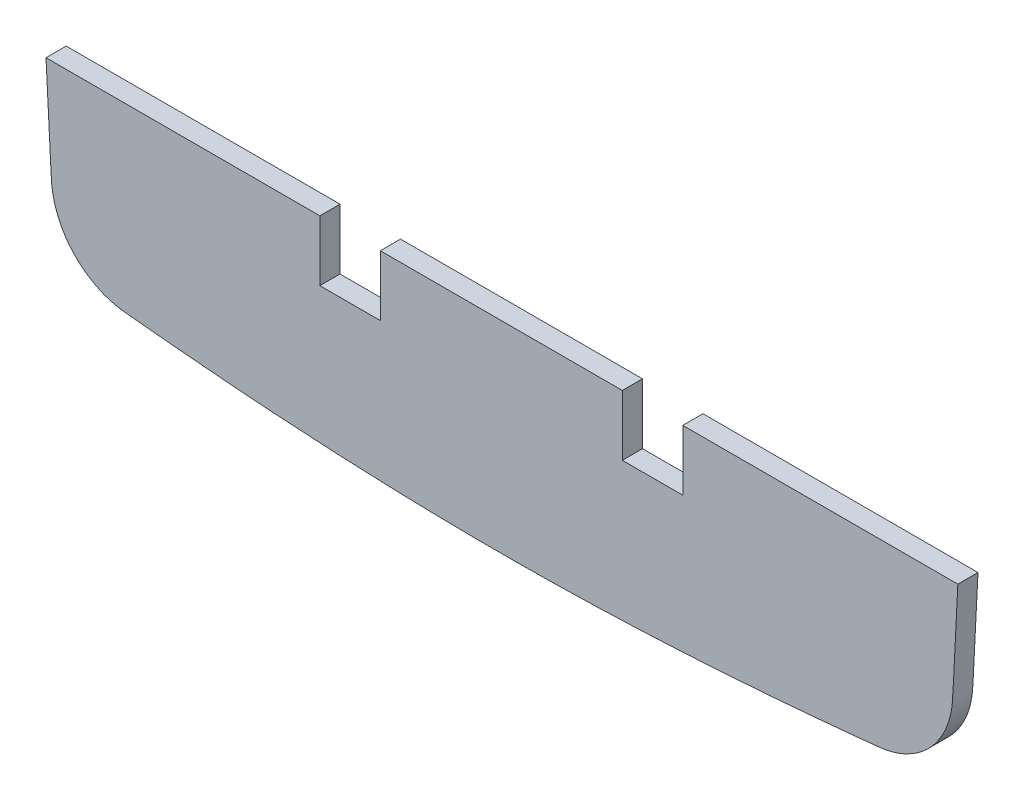
SolidWorks part; units mm, degrees
material "Balsa"
ref_plane "Front Plane" through (0, 0, 0) normal (0, 0, 1) x (1, 0, 0)
ref_plane "Top Plane" through (0, 0, 0) normal (0, 1, 0) x (1, 0, 0)
ref_plane "Right Plane" through (0, 0, 0) normal (1, 0, 0) x (0, 0, -1)
sketch "Sketch1" plane through (0, 0, 0) normal (0, 0, 1) x (1, 0, 0)
  line L0 (0, 0) -> (63.5, 0) construction
  line L1 (63.5, 0) -> (63.5, -63.8615) construction
  line L2 (63.5, 0) -> (63.5, 62.0279) construction
  line L3 (63.5, 0) -> (121.8493, 0) construction
  line L4 (5.9984, -38.4615) -> (121.0016, -38.4615)
  line L5 (48.26, -46.0815) -> (40.64, -38.4615) construction
  line L6 (78.74, -38.4615) -> (86.36, -38.4615)
  line L7 (78.74, -38.4615) -> (78.74, -46.0815)
  line L8 (78.74, -46.0815) -> (86.36, -46.0815)
  line L9 (86.36, -38.4615) -> (86.36, -46.0815)
  line L10 (78.74, -38.4615) -> (86.36, -46.0815) construction
  line L11 (78.74, -46.0815) -> (86.36, -38.4615) construction
  line L12 (48.26, -38.4615) -> (40.64, -46.0815) construction
  line L13 (40.64, -38.4615) -> (40.64, -46.0815)
  line L14 (48.26, -46.0815) -> (40.64, -46.0815)
  line L15 (48.26, -38.4615) -> (48.26, -46.0815)
  line L16 (48.26, -38.4615) -> (40.64, -38.4615)
  spline S0 degree 3 poles (63.5, 62.0279) (67.9841, 62.0313) (72.5689, 61.9603) (77.2546, 61.8087) (79.5975, 61.7328) (81.9656, 61.6369) (84.359, 61.5204) (85.5557, 61.4622) (86.7587, 61.3989) (87.9681, 61.3303) (88.5728, 61.2961) (89.1791, 61.2605) (89.787, 61.2237) (90.0909, 61.2052) (90.3952, 61.1865) (90.7, 61.1674) (90.8523, 61.1579) (91.0048, 61.1483) (91.2336, 61.1337) (91.3099, 61.1289) (91.4244, 61.1215) (91.4626, 61.1191) (91.5199, 61.1154) (91.539, 61.1142) (91.5676, 61.1123) (91.5772, 61.1117) (91.5962, 61.1105) (91.607, 61.1098) (91.6153, 61.1093) (95.9081, 60.8323) (100.3402, 60.4874) (104.9144, 60.0718) (106.0579, 59.9679) (107.2103, 59.8596) (108.3718, 59.7469) (108.9525, 59.6905) (109.5354, 59.6331) (110.1207, 59.5745) (110.4133, 59.5453) (110.7065, 59.5157) (111.0002, 59.4859) (111.1471, 59.471) (111.294, 59.457) (111.5891, 59.4207) (111.7372, 59.3991) (111.8856, 59.3739) (112.4793, 59.2732) (113.0782, 59.1159) (114.2582, 58.6819) (114.8392, 58.4041) (115.9535, 57.729) (116.4869, 57.3328) (116.981, 56.8846) (117.228, 56.6605) (117.4652, 56.4233) (117.6906, 56.174) (117.8033, 56.0494) (117.913, 55.9217) (118.0731, 55.7261) (118.1257, 55.6601) (118.2034, 55.5603) (118.2292, 55.5268) (118.2674, 55.4764) (118.2801, 55.4595) (118.2991, 55.4342) (118.3054, 55.4257) (118.3181, 55.4088) (118.3255, 55.3988) (118.3306, 55.3918) (118.9884, 54.5031) (119.5132, 53.4969) (119.8638, 52.437) (120.039, 51.9071) (120.1722, 51.3639) (120.2628, 50.8163) (120.3081, 50.5425) (120.3428, 50.2677) (120.3907, 49.7182) (120.4027, 49.444) (120.418, 49.1684) (120.5404, 46.9632) (120.6594, 44.6922) (120.8872, 40.0186) (120.996, 37.6159) (121.0977, 35.1473) (121.1486, 33.9131) (121.1977, 32.6623) (121.2448, 31.3952) (121.2683, 30.7616) (121.2914, 30.1239) (121.3139, 29.4822) (121.3251, 29.1613) (121.3363, 28.8394) (121.3472, 28.5165) (121.3527, 28.355) (121.3582, 28.1933) (121.3663, 27.9503) (121.369, 27.8693) (121.373, 27.7476) (121.3744, 27.707) (121.3764, 27.6461) (121.3771, 27.6258) (121.3781, 27.5954) (121.3784, 27.5852) (121.3789, 27.57) (121.3791, 27.5649) (121.3794, 27.5548) (121.3796, 27.5479) (121.3797, 27.5446) (121.4915, 24.1484) (121.6067, 20.0897) (121.6965, 15.3644) (121.7414, 13.0018) (121.7798, 10.4726) (121.8069, 7.7774) (121.8205, 6.4298) (121.8313, 5.0408) (121.8386, 3.6104) (121.8422, 2.8952) (121.845, 2.1697) (121.8469, 1.4339) (121.8478, 1.066) (121.8485, 0.6956) (121.8489, 0.3225) (121.8491, 0.136) (121.8493, -0.0512) (121.8495, -0.3329) (121.8495, -0.4269) (121.8495, -0.5683) (121.8495, -0.6154) (121.8495, -0.6862) (121.8495, -0.7098) (121.8495, -0.7452) (121.8495, -0.757) (121.8495, -0.7807) (121.8495, -0.7912) (121.8495, -0.8043) (121.8484, -7.4995) (121.7684, -13.2128) (121.6707, -17.9374) (121.6219, -20.2997) (121.5684, -22.4154) (121.5158, -24.2854) (121.4895, -25.2205) (121.4634, -26.0941) (121.438, -26.9066) (121.4254, -27.3128) (121.4129, -27.7038) (121.4006, -28.0794) (121.3945, -28.2673) (121.3885, -28.4513) (121.3795, -28.7216) (121.3765, -28.8107) (121.3721, -28.943) (121.3706, -28.9869) (121.3684, -29.0523) (121.3677, -29.074) (121.3666, -29.1066) (121.3662, -29.1174) (121.3657, -29.1336) (121.3655, -29.139) (121.3652, -29.1471) (121.3652, -29.1498) (121.365, -29.1539) (121.365, -29.1552) (121.3649, -29.1579) (121.3649, -29.158) (121.3648, -29.1606) (121.1857, -34.4616) (120.969, -39.4501) (120.7334, -44.1255) (120.6156, -46.4631) (120.4931, -48.7226) (120.3678, -50.9044) (120.3522, -51.1771) (120.3398, -51.4482) (120.2916, -51.991) (120.2571, -52.2624) (120.2122, -52.5325) (120.1225, -53.0727) (119.9915, -53.6079) (119.6485, -54.6514) (119.4358, -55.1596) (119.1855, -55.6466) (119.0603, -55.8901) (118.9259, -56.1283) (118.783, -56.3603) (118.7116, -56.4762) (118.638, -56.5907) (118.5246, -56.7599) (118.4863, -56.8158) (118.428, -56.8992) (118.4085, -56.9268) (118.379, -56.9682) (118.3692, -56.9819) (118.3544, -57.0025) (118.3494, -57.0094) (118.342, -57.0196) (118.3395, -57.023) (118.3345, -57.0299) (118.3327, -57.0324) (118.3295, -57.0367) (117.9239, -57.5942) (117.4643, -58.1088) (116.4608, -59.0276) (115.9181, -59.4329) (114.7838, -60.122) (114.1921, -60.4046) (112.9914, -60.8439) (112.3823, -61.0018) (111.7793, -61.1016) (111.6286, -61.1265) (111.4782, -61.1478) (111.1787, -61.1831) (111.0296, -61.1976) (110.8804, -61.2131) (110.5821, -61.2442) (110.2845, -61.2749) (109.9876, -61.3054) (109.3937, -61.3663) (108.8024, -61.4261) (108.2138, -61.4848) (107.0367, -61.602) (105.8701, -61.7147) (104.714, -61.8227) (102.4019, -62.0388) (100.1319, -62.2364) (97.9031, -62.4157) (96.7888, -62.5053) (95.6847, -62.5904) (94.591, -62.671) (94.0442, -62.7113) (93.4999, -62.7505) (92.9582, -62.7885) (92.6874, -62.8076) (92.4172, -62.8263) (92.1476, -62.8448) (92.0128, -62.854) (91.8782, -62.8632) (91.6765, -62.8769) (91.6093, -62.8814) (91.5086, -62.8882) (91.475, -62.8904) (91.4247, -62.8938) (91.4079, -62.8949) (91.3828, -62.8966) (91.3744, -62.8972) (91.3576, -62.8983) (91.3505, -62.8988) (91.3409, -62.8994) (86.3808, -63.2308) (81.5325, -63.4748) (72.0552, -63.7923) (67.4249, -63.8658) (58.3884, -63.8569) (53.7581, -63.7745) (49.0149, -63.6071) (46.6432, -63.5234) (44.2434, -63.4186) (41.8151, -63.2921) (40.6009, -63.2289) (39.3797, -63.1603) (38.1513, -63.0862) (37.5371, -63.0492) (36.9211, -63.0108) (36.3033, -62.9711) (35.9944, -62.9512) (35.6851, -62.931) (35.3753, -62.9105) (35.2204, -62.9002) (35.0654, -62.8898) (34.8327, -62.8742) (34.7552, -62.8689) (34.6387, -62.861) (34.5999, -62.8584) (34.5417, -62.8544) (34.5223, -62.8531) (34.4932, -62.8511) (34.4834, -62.8505) (34.464, -62.8492) (34.453, -62.8484) (34.4446, -62.8478) (30.1708, -62.556) (25.7295, -62.1941) (21.1169, -61.7589) (19.9638, -61.6501) (18.7999, -61.5367) (17.6252, -61.4188) (17.3315, -61.3894) (17.0372, -61.3596) (16.7421, -61.3296) (16.5946, -61.3145) (16.4469, -61.2994) (16.1512, -61.2691) (16.0033, -61.255) (15.8549, -61.2376) (15.261, -61.1681) (14.6573, -61.0422) (13.4592, -60.6706) (12.8647, -60.4247) (11.7152, -59.8076) (11.1601, -59.4375) (10.1214, -58.587) (9.6382, -58.106) (9.2059, -57.578) (8.9898, -57.314) (8.7861, -57.0386) (8.596, -56.7536) (8.5009, -56.6111) (8.4093, -56.4662) (8.2771, -56.2456) (8.2339, -56.1715) (8.1705, -56.0596) (8.1496, -56.0222) (8.1186, -55.9659) (8.1083, -55.9471) (8.093, -55.9189) (8.0879, -55.9094) (8.0803, -55.8953) (8.0777, -55.8906) (8.0726, -55.8811) (8.0696, -55.8754) (8.0676, -55.8717) (7.5645, -54.9314) (7.2046, -53.9056) (7.0044, -52.8537) (6.9543, -52.5907) (6.9141, -52.3262) (6.8534, -51.7961) (6.8362, -51.531) (6.8204, -51.2652) (6.7889, -50.7334) (6.7576, -50.1968) (6.7264, -49.6551) (6.6016, -47.4887) (6.4795, -45.2433) (6.2445, -40.5935) (6.1317, -38.1892) (6.0258, -35.7052) (5.9729, -34.4632) (5.9217, -33.2014) (5.8725, -31.9196) (5.8479, -31.2787) (5.8239, -30.6329) (5.8003, -29.9821) (5.7886, -29.6567) (5.777, -29.3301) (5.7655, -29.0022) (5.7597, -28.8382) (5.754, -28.674) (5.7455, -28.4272) (5.7427, -28.3448) (5.7385, -28.2212) (5.7371, -28.1799) (5.735, -28.118) (5.7342, -28.0974) (5.7332, -28.0664) (5.7328, -28.0561) (5.7323, -28.0406) (5.7321, -28.0355) (5.7319, -28.0277) (5.7318, -28.0252) (5.7316, -28.02) (5.7315, -28.0161) (5.7314, -28.0148) (5.6447, -25.4549) (5.5316, -21.8451) (5.4326, -17.1741) (5.3832, -14.8386) (5.3377, -12.2379) (5.3037, -9.3719) (5.2867, -7.9389) (5.2726, -6.4396) (5.2625, -4.8741) (5.2574, -4.0914) (5.2534, -3.2921) (5.2504, -2.4764) (5.249, -2.0685) (5.2478, -1.6565) (5.2469, -1.2404) (5.2465, -1.0323) (5.2461, -0.8232) (5.2458, -0.6131) (5.2457, -0.508) (5.2456, -0.4027) (5.2454, -0.2444) (5.2454, -0.1915) (5.2453, -0.1121) (5.2453, -0.0857) (5.2452, -0.0459) (5.2452, -0.0327) (5.2452, -0.0062) (5.2452, 0.0088) (5.2452, 0.0203) (5.2417, 5.9349) (5.3007, 11.233) (5.3858, 15.9061) (5.4284, 18.2427) (5.4776, 20.4233) (5.5297, 22.4481) (5.5558, 23.4606) (5.5826, 24.4341) (5.6097, 25.3687) (5.6233, 25.8361) (5.637, 26.2937) (5.6507, 26.7416) (5.6575, 26.9656) (5.6644, 27.1871) (5.6713, 27.4062) (5.6747, 27.5158) (5.6781, 27.6247) (5.6833, 27.7872) (5.685, 27.8412) (5.6876, 27.922) (5.6884, 27.9489) (5.6897, 27.9892) (5.6901, 28.0026) (5.6908, 28.0228) (5.691, 28.0295) (5.6913, 28.0395) (5.6914, 28.0429) (5.6916, 28.0496) (5.6917, 28.0513) (5.6919, 28.0563) (5.8561, 33.181) (6.0559, 38.0523) (6.2757, 42.668) (6.3856, 44.9759) (6.5006, 47.22) (6.6189, 49.4005) (6.6337, 49.6731) (6.6516, 49.9453) (6.7143, 50.4901) (6.7561, 50.7622) (6.8084, 51.0329) (6.9131, 51.5742) (7.0595, 52.1097) (7.4351, 53.152) (7.6651, 53.6587) (7.9326, 54.143) (8.0663, 54.3851) (8.2094, 54.6217) (8.361, 54.8517) (8.4368, 54.9667) (8.5147, 55.0801) (8.6347, 55.2475) (8.6752, 55.3029) (8.7367, 55.3853) (8.7574, 55.4126) (8.7885, 55.4535) (8.7989, 55.467) (8.8146, 55.4874) (8.8198, 55.4942) (8.8303, 55.5077) (8.8343, 55.5129) (8.8408, 55.5212) (9.2536, 56.0518) (9.7169, 56.539) (10.7195, 57.4068) (11.2579, 57.7882) (11.8181, 58.1108) (12.9386, 58.7559) (14.1459, 59.1572) (15.3258, 59.3334) (15.6208, 59.3775) (15.9134, 59.4043) (16.498, 59.4644) (16.7898, 59.4941) (17.081, 59.5236) (17.6635, 59.5826) (18.2437, 59.6404) (18.8217, 59.6972) (19.9777, 59.8108) (21.1248, 59.92) (22.2631, 60.0248) (24.5398, 60.2344) (26.7813, 60.4266) (28.9881, 60.6014) (30.0916, 60.6888) (31.1863, 60.7718) (32.2725, 60.8506) (32.8155, 60.89) (33.3564, 60.9284) (33.8951, 60.9656) (34.1645, 60.9843) (34.4333, 61.0026) (34.7016, 61.0207) (34.8358, 61.0298) (34.9698, 61.0388) (35.1706, 61.0522) (35.2375, 61.0566) (35.3378, 61.0633) (35.3712, 61.0655) (35.4214, 61.0688) (35.4381, 61.0699) (35.4631, 61.0715) (35.4715, 61.0721) (35.4882, 61.0732) (35.4954, 61.0737) (35.5049, 61.0743) (45.2376, 61.7146) (54.5678, 62.0211) (63.5, 62.0279) (67.9841, 62.0313) (72.5689, 61.9603) knots -0.004975 0 0 0 0.004975 0.004975 0.004975 0.00995 0.00995 0.00995 0.014925 0.014925 0.014925 0.0199 0.0199 0.0199 0.024876 0.024876 0.024876 0.029851 0.029851 0.034826 0.034826 0.039801 0.039801 0.044776 0.044776 0.049751 0.049751 0.054726 0.054726 0.054726 0.059701 0.059701 0.059701 0.064677 0.064677 0.064677 0.069652 0.069652 0.069652 0.074627 0.074627 0.074627 0.079602 0.079602 0.084577 0.084577 0.084577 0.089552 0.089552 0.094527 0.094527 0.099502 0.099502 0.099502 0.104478 0.104478 0.104478 0.109453 0.109453 0.114428 0.114428 0.119403 0.119403 0.124378 0.124378 0.129353 0.129353 0.134328 0.134328 0.134328 0.139303 0.139303 0.139303 0.144279 0.144279 0.144279 0.149254 0.149254 0.154229 0.154229 0.154229 0.159204 0.159204 0.164179 0.164179 0.164179 0.169154 0.169154 0.169154 0.174129 0.174129 0.174129 0.179104 0.179104 0.179104 0.18408 0.18408 0.189055 0.189055 0.19403 0.19403 0.199005 0.199005 0.20398 0.20398 0.208955 0.208955 0.21393 0.21393 0.21393 0.218905 0.218905 0.218905 0.223881 0.223881 0.223881 0.228856 0.228856 0.228856 0.233831 0.233831 0.233831 0.238806 0.238806 0.238806 0.243781 0.243781 0.248756 0.248756 0.253731 0.253731 0.258706 0.258706 0.263682 0.263682 0.268657 0.268657 0.268657 0.273632 0.273632 0.273632 0.278607 0.278607 0.278607 0.283582 0.283582 0.283582 0.288557 0.288557 0.288557 0.293532 0.293532 0.298507 0.298507 0.303483 0.303483 0.308458 0.308458 0.313433 0.313433 0.318408 0.318408 0.323383 0.323383 0.328358 0.328358 0.333333 0.333333 0.333333 0.338308 0.338308 0.338308 0.343284 0.343284 0.343284 0.348259 0.348259 0.353234 0.353234 0.353234 0.358209 0.358209 0.363184 0.363184 0.363184 0.368159 0.368159 0.368159 0.373134 0.373134 0.378109 0.378109 0.383085 0.383085 0.38806 0.38806 0.393035 0.393035 0.39801 0.39801 0.402985 0.402985 0.402985 0.40796 0.40796 0.412935 0.412935 0.41791 0.41791 0.422886 0.422886 0.422886 0.427861 0.427861 0.432836 0.432836 0.432836 0.437811 0.437811 0.437811 0.442786 0.442786 0.442786 0.447761 0.447761 0.447761 0.452736 0.452736 0.452736 0.457711 0.457711 0.457711 0.462687 0.462687 0.462687 0.467662 0.467662 0.467662 0.472637 0.472637 0.477612 0.477612 0.482587 0.482587 0.487562 0.487562 0.492537 0.492537 0.497512 0.497512 0.497512 0.502488 0.502488 0.507463 0.507463 0.512438 0.512438 0.512438 0.517413 0.517413 0.517413 0.522388 0.522388 0.522388 0.527363 0.527363 0.527363 0.532338 0.532338 0.532338 0.537313 0.537313 0.542289 0.542289 0.547264 0.547264 0.552239 0.552239 0.557214 0.557214 0.562189 0.562189 0.562189 0.567164 0.567164 0.567164 0.572139 0.572139 0.572139 0.577114 0.577114 0.577114 0.58209 0.58209 0.587065 0.587065 0.587065 0.59204 0.59204 0.597015 0.597015 0.60199 0.60199 0.606965 0.606965 0.606965 0.61194 0.61194 0.61194 0.616915 0.616915 0.621891 0.621891 0.626866 0.626866 0.631841 0.631841 0.636816 0.636816 0.641791 0.641791 0.646766 0.646766 0.646766 0.651741 0.651741 0.651741 0.656716 0.656716 0.661692 0.661692 0.661692 0.666667 0.666667 0.666667 0.671642 0.671642 0.676617 0.676617 0.676617 0.681592 0.681592 0.681592 0.686567 0.686567 0.686567 0.691542 0.691542 0.691542 0.696517 0.696517 0.701493 0.701493 0.706468 0.706468 0.711443 0.711443 0.716418 0.716418 0.721393 0.721393 0.726368 0.726368 0.731343 0.731343 0.731343 0.736318 0.736318 0.736318 0.741294 0.741294 0.741294 0.746269 0.746269 0.746269 0.751244 0.751244 0.751244 0.756219 0.756219 0.756219 0.761194 0.761194 0.761194 0.766169 0.766169 0.771144 0.771144 0.776119 0.776119 0.781095 0.781095 0.78607 0.78607 0.78607 0.791045 0.791045 0.791045 0.79602 0.79602 0.79602 0.800995 0.800995 0.800995 0.80597 0.80597 0.80597 0.810945 0.810945 0.810945 0.81592 0.81592 0.820896 0.820896 0.825871 0.825871 0.830846 0.830846 0.835821 0.835821 0.840796 0.840796 0.845771 0.845771 0.845771 0.850746 0.850746 0.850746 0.855721 0.855721 0.855721 0.860697 0.860697 0.865672 0.865672 0.865672 0.870647 0.870647 0.875622 0.875622 0.875622 0.880597 0.880597 0.880597 0.885572 0.885572 0.890547 0.890547 0.895522 0.895522 0.900498 0.900498 0.905473 0.905473 0.910448 0.910448 0.910448 0.915423 0.915423 0.920398 0.920398 0.920398 0.925373 0.925373 0.925373 0.930348 0.930348 0.935323 0.935323 0.935323 0.940299 0.940299 0.940299 0.945274 0.945274 0.945274 0.950249 0.950249 0.950249 0.955224 0.955224 0.955224 0.960199 0.960199 0.960199 0.965174 0.965174 0.965174 0.970149 0.970149 0.975124 0.975124 0.9801 0.9801 0.985075 0.985075 0.99005 0.99005 0.995025 0.995025 0.995025 1 1 1 1.004975 1.004975 1.004975 only from (63.5, 62.0279) to (63.5, 62.0279)
  point P4 (63.5, -38.4615)
  point P7 (5.2452, 0)
  point P11 (63.5, -38.4615)
  point P15 (82.55, -42.2715)
  point P20 (44.45, -42.2715)
  dimension "D1" = 63.5
  dimension "D2" = 63.8615
  dimension "D3" = 58.2548
  dimension "D4" = 38.4615
  dimension "D5" = 15.24
  dimension "D6" = 7.62
  dimension "D7" = 7.62
extrude "Boss-Extrude1" add sketch "Sketch1" along normal blind 2.54 contours S0 L4 L9 L8 L7 L15 L14 L13 region at (64.1934, -50.0829, 0)
